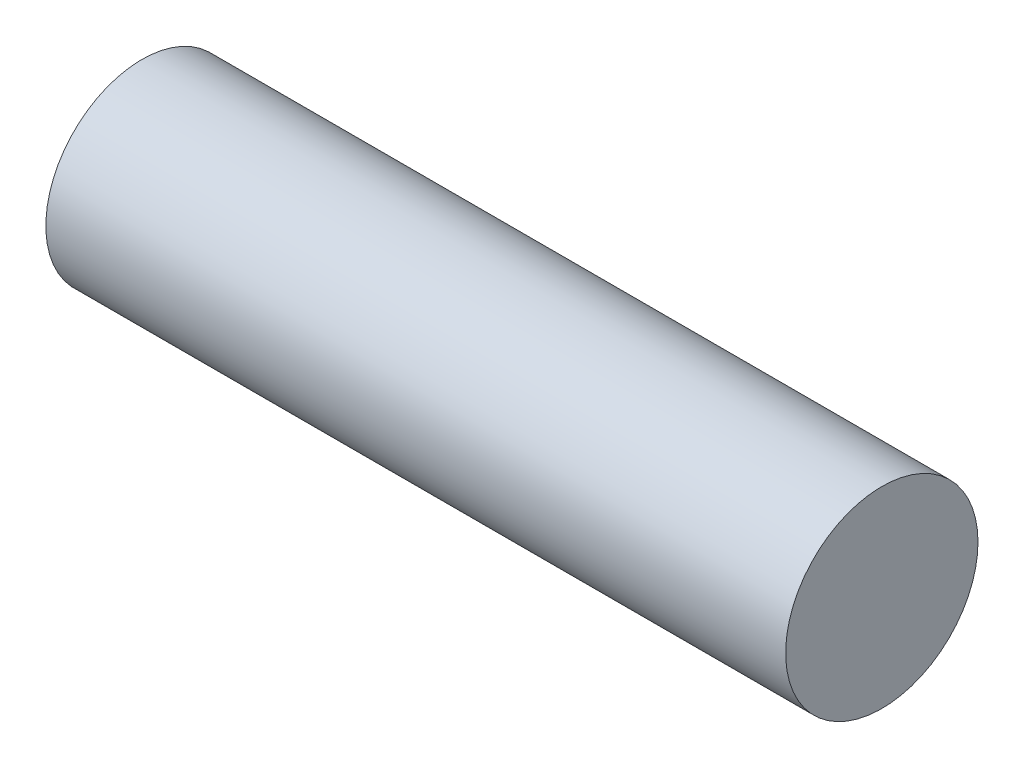
SolidWorks part; units mm, degrees
ref_plane "Front Plane" through (0, 0, 0) normal (0, 0, 1) x (1, 0, 0)
ref_plane "Top Plane" through (0, 0, 0) normal (0, 1, 0) x (1, 0, 0)
ref_plane "Right Plane" through (0, 0, 0) normal (1, 0, 0) x (0, 0, -1)
sketch "Sketch1" plane through (0, 0, 0) normal (1, 0, 0) x (0, 0, -1)
  circle A0 centre (0, 0) radius 250
  dimension "D1" = 500
extrude "Extrude-Thin1" add sketch "Sketch1" along normal blind 2000 thin thin type one direction wall 10
ref_axis "Axis1" through (1102.4215, 0, 0) along (-1, 0, 0)
extrude "Boss-Extrude1" add sketch "Sketch1<2>" along normal blind 10 from offset 1990
sketch "Sketch1<2>" plane through (0, 0, 0) normal (1, 0, 0) x (0, 0, -1) same geometry as "Sketch1"
extrude "Boss-Extrude2" add sketch "Sketch1<3>" along normal blind 10
sketch "Sketch1<3>" plane through (0, 0, 0) normal (1, 0, 0) x (0, 0, -1) same geometry as "Sketch1"
